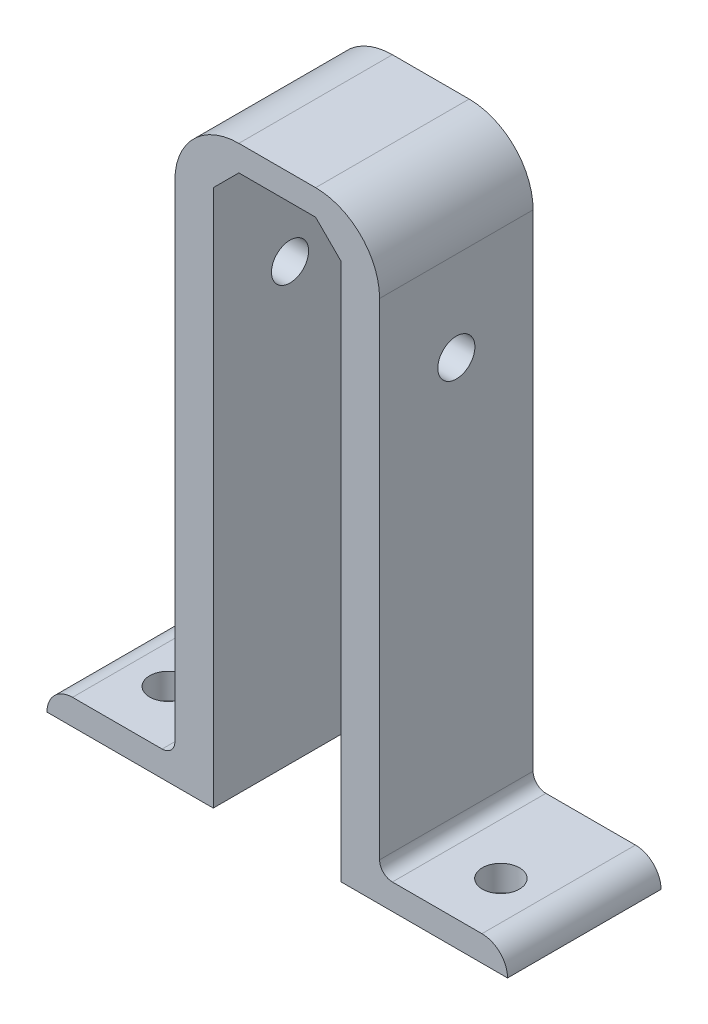
SolidWorks part; units mm, degrees
ref_plane "前视基准面" through (0, 0, 0) normal (0, 0, 1) x (1, 0, 0)
ref_plane "上视基准面" through (0, 0, 0) normal (0, 1, 0) x (1, 0, 0)
ref_plane "右视基准面" through (0, 0, 0) normal (1, 0, 0) x (0, 0, -1)
sketch "草图1" plane through (0, 0, 0) normal (0, 0, 1) x (1, 0, 0)
  line L0 (0, 0) -> (13, 0)
  line L1 (13, 0) -> (13, 44)
  line L2 (13, 44) -> (23, 44)
  line L8 (26, 46) -> (10, 46)
  line L9 (10, 46) -> (10, 2)
  line L10 (10, 2) -> (0, 2)
  line L11 (0, 2) -> (0, 0)
  line L18 (18, 46) -> (18, 44) construction
  line L19 (36, 2) -> (36, 0)
  line L20 (26, 2) -> (36, 2)
  line L21 (26, 46) -> (26, 2)
  line L22 (23, 0) -> (23, 44)
  line L23 (36, 0) -> (23, 0)
  dimension "D1" = 10
  dimension "D3" = 2
  dimension "D4" = 2
  dimension "D6" = 44
  dimension "D9" = 13
extrude "凸台-拉伸1" add sketch "草图1" along normal blind 12
sketch "草图2" plane through (13, 0, 0) normal (1, 0, 0) x (0, 0, -1)
  line L0 (-12, 0) -> (-12, 34) construction
  line L2 (-12, 34) -> (-6, 34) construction
  circle A0 centre (-6, 34) radius 1.45
  dimension "D3" = 2.9
  dimension "D1" = 34
  dimension "D2" = 6
extrude "切除-拉伸1" cut sketch "草图2" against normal blind 15 and the other way blind 15
sketch "草图3" plane through (0, 2, 0) normal (0, 1, 0) x (1, 0, 0)
  line L0 (5, 0) -> (5, -7.5192) construction
  line L1 (10, 0) -> (0, 0) construction
  line L2 (18, 0) -> (18, -3.8379) construction
  line L3 (26, 0) -> (10, 0) construction
  circle A0 centre (5, -7.5192) radius 1.45
  circle A1 centre (31, -7.5192) radius 1.45
  dimension "D1" = 2.9
extrude "切除-拉伸2" cut sketch "草图3" against normal blind 15
fillet "圆角1" radius 1 2 edges at (26, 2, 6) (10, 2, 6)
fillet "圆角2" radius 5 2 edges at (26, 46, 6) (10, 46, 6)
fillet "圆角3" radius 2 2 edges at (36, 2, 6) (0, 2, 6)
chamfer "倒角1" distance 2 angle 45 2 edges at (13, 44, 6) (23, 44, 6)
